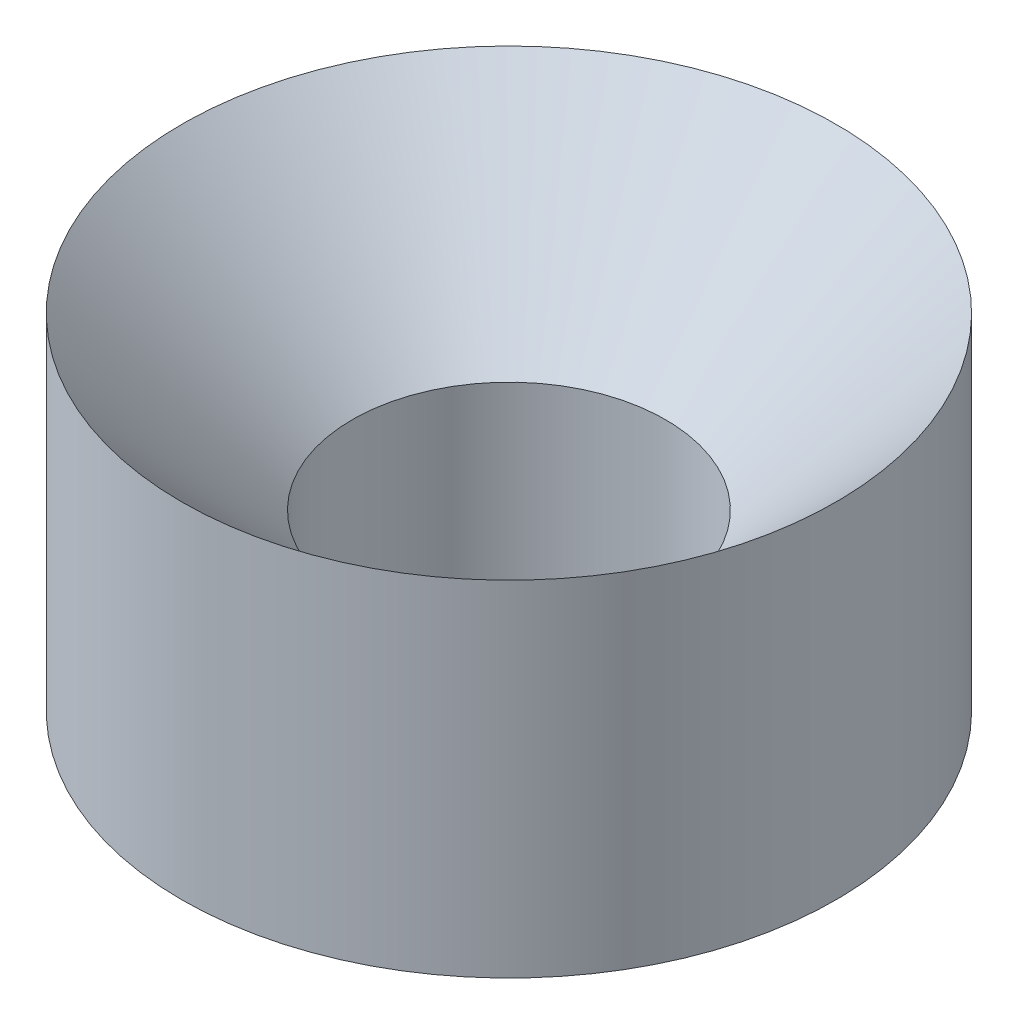
SolidWorks part; units mm, degrees
ref_plane "Front Plane" through (0, 0, 0) normal (0, 0, 1) x (1, 0, 0)
ref_plane "Top Plane" through (0, 0, 0) normal (0, 1, 0) x (1, 0, 0)
ref_plane "Right Plane" through (0, 0, 0) normal (1, 0, 0) x (0, 0, -1)
sketch "Sketch1" plane through (0, 0, 0) normal (0, 1, 0) x (1, 0, 0)
  circle A0 centre (0, 0) radius 4.7
  dimension "D1" = 9.4
extrude "Boss-Extrude1" add sketch "Sketch1" along normal blind 5
sketch "Sketch2" plane through (0, 5, 0) normal (0, 1, 0) x (1, 0, 0)
  circle A0 centre (0, 0) radius 2.25
  dimension "D1" = 4.5
extrude "Cut-Extrude1" cut sketch "Sketch2" against normal through all
chamfer "Chamfer1" distance 2.5 angle 45 1 edges at (0, 5, 2.25)
